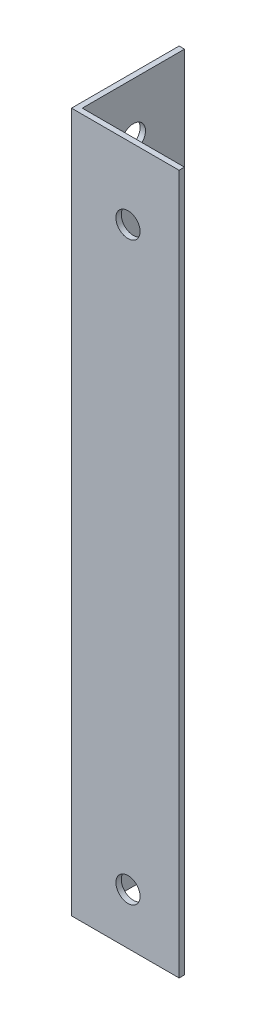
SolidWorks part; units mm, degrees
material "1060 Сплав"
ref_plane "Спереди" through (0, 0, 0) normal (0, 0, 1) x (1, 0, 0)
ref_plane "Сверху" through (0, 0, 0) normal (0, 1, 0) x (1, 0, 0)
ref_plane "Справа" through (0, 0, 0) normal (1, 0, 0) x (0, 0, -1)
sketch "Эскиз1" plane through (0, 0, 0) normal (0, 1, 0) x (1, 0, 0)
  line L0 (0, 0) -> (0, 20)
  line L1 (0, 20) -> (1, 20)
  line L2 (1, 20) -> (1, 1)
  line L3 (1, 1) -> (20, 1)
  line L4 (20, 1) -> (20, 0)
  line L5 (20, 0) -> (0, 0)
  dimension "D1" = 1
  dimension "D2" = 20
extrude "Бобышка-Вытянуть1" add sketch "Эскиз1" along normal blind 130
sketch "Эскиз2" plane through (0, 0, -1) normal (0, 0, -1) x (-1, 0, 0)
  circle A0 centre (-10.5, 9.5) radius 2.25 construction
  circle A1 centre (-10.5, 9.5) radius 2.25
extrude "Вырез-Вытянуть1" cut sketch "Эскиз2" against normal through all
sketch "Эскиз3" plane through (0, 0, -1) normal (0, 0, -1) x (-1, 0, 0)
  line L0 (0, 130) -> (0, 0) construction
  line L1 (0, 130) -> (-20, 130) construction
  circle A1 centre (-10.5, 116.5) radius 2.25
  dimension "D1" = 10.5
  dimension "D2" = 13.5
  dimension "D3" = 4.5
extrude "Вырез-Вытянуть2" cut sketch "Эскиз3" against normal through all
sketch "Эскиз4" plane through (1, 0, 0) normal (1, 0, 0) x (0, 0, -1)
  line L0 (10.5, 130) -> (10.5, 120.5) construction
  line L1 (1, 130) -> (20, 130) construction
  circle A0 centre (10.5, 120.5) radius 2.25
  dimension "D2" = 4.5
  dimension "D1" = 9.5
extrude "Вырез-Вытянуть3" cut sketch "Эскиз4" against normal through all
sketch "Эскиз5" plane through (1, 0, 0) normal (1, 0, 0) x (0, 0, -1)
  line L0 (10.5, 0) -> (10.5, 9.5) construction
  line L1 (1, 0) -> (20, 0) construction
  circle A0 centre (10.5, 9.5) radius 2.25
  dimension "D1" = 4.5
  dimension "D2" = 9.5
extrude "Вырез-Вытянуть4" cut sketch "Эскиз5" against normal through all
